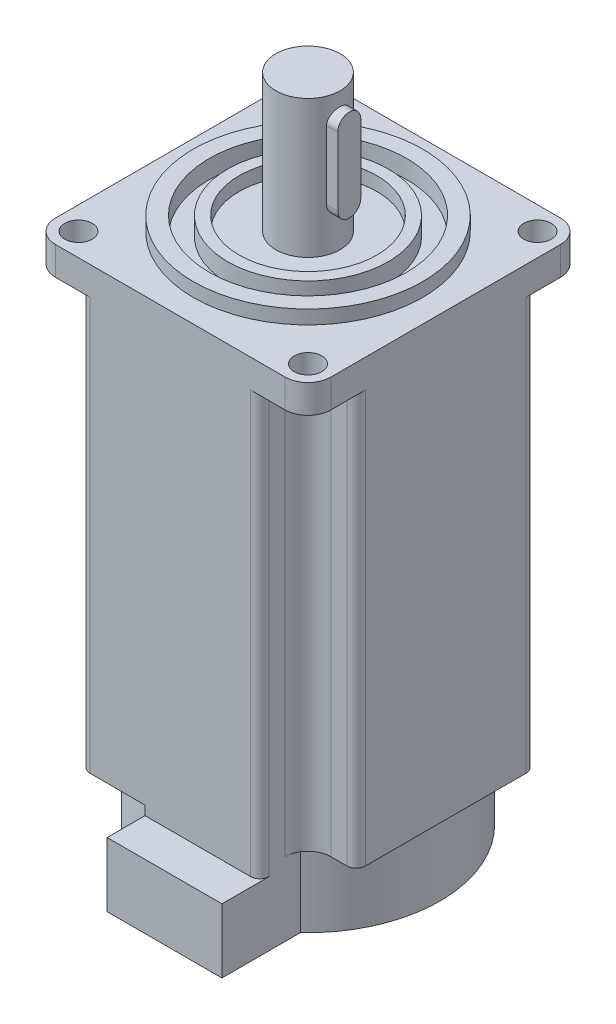
SolidWorks part; units mm, degrees
ref_plane "前基準面" through (0, 0, 0) normal (0, 0, 1) x (1, 0, 0)
ref_plane "上基準面" through (0, 0, 0) normal (0, 1, 0) x (1, 0, 0)
ref_plane "右基準面" through (0, 0, 0) normal (1, 0, 0) x (0, 0, -1)
sketch "草圖1" plane through (0, 0, 0) normal (0, 1, 0) x (1, 0, 0)
  line L0 (-19.5, -24.75) -> (-30, -24.75) construction
  line L5 (-30, -30) -> (30, -30)
  line L6 (-30, -30) -> (-30, 30)
  line L11 (-30, 30) -> (30, 30)
  line L12 (30, -30) -> (30, 30)
  line L13 (0, 30) -> (0, -30) construction
  line L14 (-30, 0) -> (30, 0) construction
  line L15 (-30, -30) -> (-19.5, -30)
  line L16 (-30, -30) -> (-30, -19.5)
  line L17 (-30, -19.5) -> (-19.5, -19.5)
  line L18 (-19.5, -30) -> (-19.5, -19.5)
  circle A1 centre (0, 0) radius 25
  circle A2 centre (0, 0) radius 21.5
  circle A3 centre (0, 0) radius 17.5
  circle A4 centre (0, 0) radius 15
  circle A5 centre (0, 0) radius 7
  point P0 (0, 0)
  dimension "D4" = 50
  dimension "D5" = 43
  dimension "D6" = 35
  dimension "D7" = 30
  dimension "D8" = 14
  dimension "D1" = 60
  dimension "D2" = 60
  dimension "D3" = 10.5
sketch "草圖2" plane through (0, 0, 0) normal (0, 1, 0) x (1, 0, 0)
  line L0 (-30, 30) -> (30, 30) construction
  line L1 (-30, -30) -> (-30, 30) construction
  line L2 (30, -30) -> (30, 30) construction
  line L3 (-30, -30) -> (30, -30) construction
  line L4 (-30, 30) -> (30, 30)
  line L5 (-30, -30) -> (-30, 30)
  line L6 (30, -30) -> (30, 30)
  line L7 (-30, -30) -> (30, -30)
extrude "填料-伸長1" add sketch "草圖2" against normal blind 96
sketch "草圖3" plane through (0, 0, 0) normal (0, 1, 0) x (1, 0, 0)
  line L0 (-30, -19.5) -> (-19.5, -19.5) construction
  line L1 (-30, -30) -> (-30, -19.5) construction
  line L2 (-19.5, -30) -> (-19.5, -19.5) construction
  line L3 (-30, -30) -> (-19.5, -30) construction
  line L4 (-30, -19.5) -> (-19.5, -19.5)
  line L5 (-30, -30) -> (-30, -19.5)
  line L6 (-19.5, -30) -> (-19.5, -19.5)
  line L7 (-30, -30) -> (-19.5, -30)
extrude "除料-伸長1" cut sketch "草圖3" against normal through all
ref_axis "基準軸1" through (0, 4.55, 0) along (0, -1, 0)
pattern_circular "環狀複製排列1" count 4 every 90 about axis through (0, 4.55, 0) along (0, -1, 0) of "除料-伸長1"
sketch "草圖4" plane through (0, 0, 0) normal (0, 1, 0) x (1, 0, 0)
  line L8 (-30, 30) -> (30, 30) construction
  line L9 (-30, -30) -> (-30, 30) construction
  line L10 (30, -30) -> (30, 30) construction
  line L11 (-30, -30) -> (30, -30) construction
  line L36 (-30, 30) -> (30, 30)
  line L37 (-30, -30) -> (-30, 30)
  line L38 (30, -30) -> (30, 30)
  line L39 (-30, -30) -> (30, -30)
extrude "填料-伸長2" add sketch "草圖4" against normal blind 6.2
sketch "草圖5" plane through (0, 0, 0) normal (0, 1, 0) x (1, 0, 0)
  circle A1 centre (0, 0) radius 25 construction
  circle A3 centre (0, 0) radius 25
extrude "填料-伸長3" add sketch "草圖5" along normal blind 3
sketch "草圖8" plane through (0, 3, 0) normal (0, 1, 0) x (1, 0, 0)
  circle A0 centre (0, 0) radius 17.5 construction
  circle A1 centre (0, 0) radius 17.5
  circle A2 centre (0, 0) radius 21.5 construction
  circle A3 centre (0, 0) radius 21.5
extrude "除料-伸長3" cut sketch "草圖8" against normal blind 4
sketch "草圖9" plane through (0, 3, 0) normal (0, 1, 0) x (1, 0, 0)
  circle A0 centre (0, 0) radius 15 construction
  circle A1 centre (0, 0) radius 15
extrude "除料-伸長4" cut sketch "草圖9" against normal blind 3
sketch "草圖10" plane through (0, 0, 0) normal (0, 1, 0) x (1, 0, 0)
  circle A0 centre (0, 0) radius 7 construction
  circle A1 centre (0, 0) radius 7
extrude "填料-伸長5" add sketch "草圖10" along normal blind 30
fillet "圓角1" radius 5 4 edges at (-19.5, -51.1, -19.5) (19.5, -51.1, -19.5) (-19.5, -51.1, 19.5) (19.5, -51.1, 19.5)
fillet "圓角2" radius 2 8 edges at (-30, -51.1, -19.5) (-19.5, -51.1, -30) (19.5, -51.1, -30) (30, -51.1, -19.5) (30, -51.1, 19.5) (19.5, -51.1, 30) (-19.5, -51.1, 30) (-30, -51.1, 19.5)
fillet "圓角3" radius 5 4 edges at (30, -3.1, -30) (30, -3.1, 30) (-30, -3.1, 30) (-30, -3.1, -30)
sketch "草圖12" plane through (0, -96, 0) normal (0, -1, 0) x (1, 0, 0)
  line L0 (-30, 0) -> (30, 0) construction
  line L6 (-5.5, 38.25) -> (19.5, 38.25)
  line L7 (-5.5, 38.25) -> (-5.5, 21.1261)
  line L8 (-5.5, 21.1261) -> (19.5, 21.1261)
  line L9 (19.5, 38.25) -> (19.5, 21.1261)
  line L11 (19.5, 24.5) -> (19.5, 28) construction
  circle A0 centre (0, 0) radius 28.75
  dimension "D1" = 57.5
  dimension "D2" = 67
  dimension "D4" = 25
sketch "草圖13" plane through (0, -96, 0) normal (0, -1, 0) x (1, 0, 0)
  circle A0 centre (0, 0) radius 28.75 construction
  circle A1 centre (0, 0) radius 28.75
extrude "填料-伸長6" add sketch "草圖13" along normal blind 16
sketch "草圖14" plane through (0, -96, 0) normal (0, -1, 0) x (1, 0, 0)
  line L0 (-5.5, 38.25) -> (19.5, 38.25) construction
  line L1 (19.5, 38.25) -> (19.5, 21.1261) construction
  line L2 (-5.5, 21.1261) -> (19.5, 21.1261) construction
  line L3 (-5.5, 38.25) -> (-5.5, 21.1261) construction
  line L4 (-5.5, 38.25) -> (19.5, 38.25)
  line L5 (19.5, 38.25) -> (19.5, 21.1261)
  line L6 (-5.5, 21.1261) -> (19.5, 21.1261)
  line L7 (-5.5, 38.25) -> (-5.5, 21.1261)
extrude "填料-伸長7" add sketch "草圖14" against normal blind 14 from surface starting at face at (0, -112, -28.75)
sketch "草圖15" plane through (0, -98, 0) normal (0, 1, 0) x (1, 0, 0)
  line L0 (-30, -30) -> (30, -30) construction
  line L1 (-5.5, -30) -> (17.5, -30)
  line L3 (-5.5, -28.219) -> (-5.5, -38.25)
  line L4 (-5.5, -38.25) -> (19.5, -38.25)
  line L5 (19.5, -38.25) -> (19.5, -21.1261)
  line L6 (-5.5, -28.219) -> (-5.5, -30)
  line L8 (19.5, -28) -> (19.5, -21.1261)
  arc A1 (-5.5, -28.219) -> (19.5, -21.1261) centre (0, 0) ccw
  arc A2 (-5.5, -28.219) -> (19.5, -21.1261) centre (0, 0) ccw
  arc A3 (17.5, -30) -> (19.5, -28) centre (17.5, -28) ccw construction
  arc A4 (17.5, -30) -> (19.5, -28) centre (17.5, -28) ccw
  dimension "D1" = 0
extrude "填料-伸長8" add sketch "草圖15" along normal up to surface (2 mm away) up to face at (0, -96, -28.75)
hole_wizard "Ø6.0 (6) 直徑孔1" positions "草圖17" profile "草圖18" hole size "Ø6.0" standard "JIS" end condition through all
sketch "草圖17" plane through (0, 0, 0) normal (0, 1, 0) x (1, 0, 0)
  point P0 (-25, 25)
  point P3 (25, 25)
  point P6 (25, -25)
  point P9 (-25, -25)
sketch "草圖18" plane through (-25, 0, -25) normal (1, 0, 0) x (0, 0, 1)
  line L0 (0, 0) -> (0, 112)
  line L1 (0, 112) -> (3, 112)
  line L2 (3, 112) -> (3, 0)
  line L5 (3, 0) -> (0, 0)
  line L11 (0, -6.35) -> (0, 107.95) construction
  dimension "貫穿孔直徑" = 6
  dimension "貫穿孔深度" = 112
sketch "草圖19" plane through (0, 30, 0) normal (0, 1, 0) x (1, 0, 0)
  line L0 (0, 0) -> (7, 0) construction
  line L1 (-30, 0) -> (30, 0) construction
  circle A0 centre (0, 0) radius 7 construction
ref_plane "平面2" through (7, 0, 0) normal (1, 0, 0) x (0, 0, -1)
sketch "草圖20" plane through (7, 0, 0) normal (1, 0, 0) x (0, 0, -1)
  line L0 (0, 24.5) -> (0, 9.5) construction
  line L1 (0, 4.55) -> (0, -95.55) construction
  line L3 (-2.5, 24.5) -> (-2.5, 9.5)
  line L4 (2.5, 24.5) -> (2.5, 9.5)
  line L5 (7, 30) -> (-7, 30) construction
  arc A0 (-2.5, 24.5) -> (2.5, 24.5) centre (0, 24.5) cw
  arc A1 (-2.5, 9.5) -> (2.5, 9.5) centre (0, 9.5) ccw
  point P11 (0, 27)
  point P12 (0, 7)
  dimension "D3" = 2.5
  dimension "D1" = 3
  dimension "D2" = 20
  dimension "D4" = 2.5
extrude "除料-伸長5" cut sketch "草圖20" against normal blind 3
sketch "草圖21" plane through (4, 0, 0) normal (1, 0, 0) x (0, 0, -1)
  line L2 (-2.5, 24.5) -> (-2.5, 9.5)
  line L3 (2.5, 9.5) -> (2.5, 24.5)
  line L4 (-2.5, 24.5) -> (-2.5, 9.5)
  line L5 (2.5, 9.5) -> (2.5, 24.5)
  arc A2 (2.5, 24.5) -> (-2.5, 24.5) centre (0, 24.5) ccw
  arc A3 (-2.5, 9.5) -> (2.5, 9.5) centre (0, 9.5) ccw
  arc A4 (2.5, 24.5) -> (-2.5, 24.5) centre (0, 24.5) ccw
  arc A5 (-2.5, 9.5) -> (2.5, 9.5) centre (0, 9.5) ccw
  dimension "D1" = 0
extrude "填料-伸長9" add sketch "草圖21" along normal blind 5
ref_plane "平面1" through (7, 0, 0) normal (1, 0, 0) x (0, 0, -1)
ref_axis "基準軸2" through (0, 0, -30) along (0, 0, 1)
